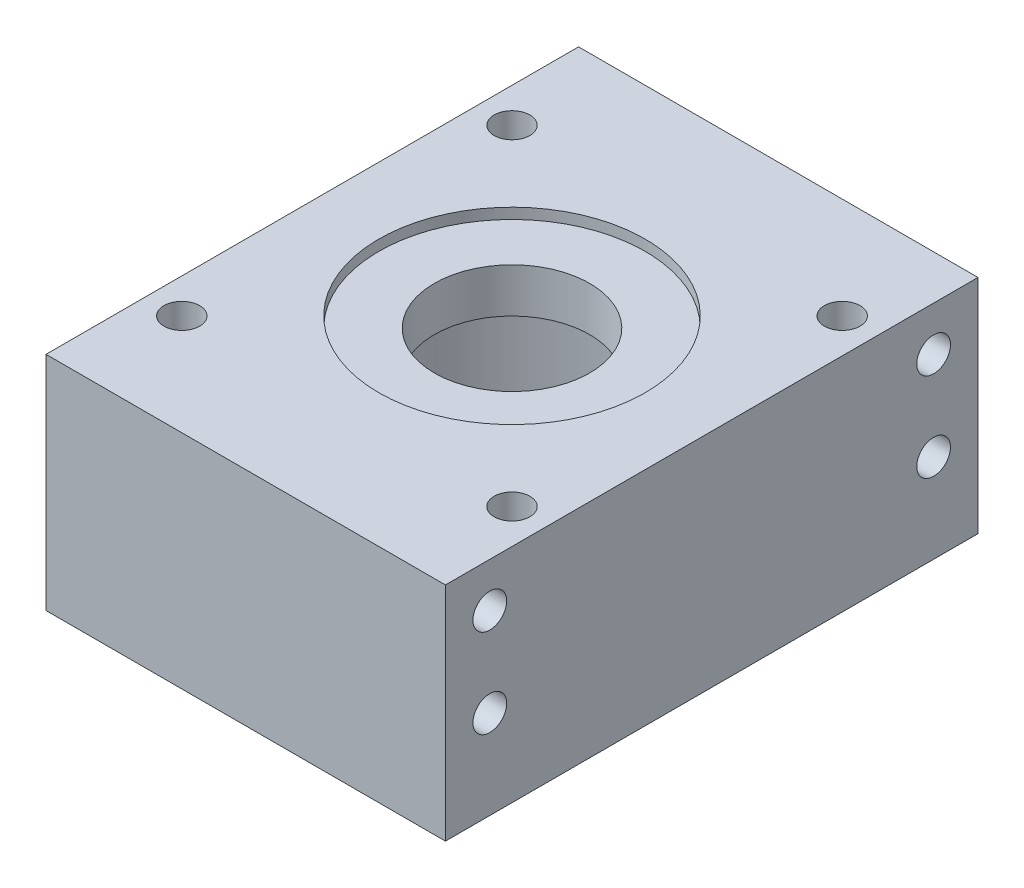
SolidWorks part; units mm, degrees
material "6061 Alloy"
ref_plane "Front" through (0, 0, 0) normal (0, 0, 1) x (1, 0, 0)
ref_plane "Top" through (0, 0, 0) normal (0, 1, 0) x (1, 0, 0)
ref_plane "Right" through (0, 0, 0) normal (1, 0, 0) x (0, 0, -1)
sketch "Sketch1" plane through (0, 0, 0) normal (0, 1, 0) x (1, 0, 0)
  line L0 (-28.575, 28.575) -> (-28.575, 38.1)
  line L1 (-28.575, 28.575) -> (28.575, 28.575) construction
  line L2 (-28.575, 28.575) -> (-28.575, -28.575)
  line L3 (-28.575, -28.575) -> (28.575, -28.575) construction
  line L4 (28.575, 28.575) -> (28.575, -28.575)
  line L5 (-28.575, 28.575) -> (28.575, -28.575) construction
  line L6 (-28.575, -28.575) -> (28.575, 28.575) construction
  line L7 (-23.622, 23.622) -> (23.622, 23.622) construction
  line L8 (-23.622, 23.622) -> (-23.622, -23.622) construction
  line L9 (-23.622, -23.622) -> (23.622, -23.622) construction
  line L10 (23.622, 23.622) -> (23.622, -23.622) construction
  line L11 (-23.622, 23.622) -> (23.622, -23.622) construction
  line L12 (-23.622, -23.622) -> (23.622, 23.622) construction
  line L13 (-28.575, 38.1) -> (28.575, 38.1)
  line L14 (28.575, 38.1) -> (28.575, 28.575)
  line L15 (-28.575, -28.575) -> (-28.575, -38.1)
  line L16 (-28.575, -38.1) -> (28.575, -38.1)
  line L17 (28.575, -38.1) -> (28.575, -28.575)
  circle A0 centre (23.622, -23.622) radius 2.5527
  circle A1 centre (23.622, 23.622) radius 2.5527
  circle A2 centre (-23.622, 23.622) radius 2.5527
  circle A3 centre (-23.622, -23.622) radius 2.5527
  point P0 (0, 0)
  point P6 (0, 0)
  dimension "D3" = 5.1054
  dimension "D1" = 57.15
  dimension "D2" = 47.244
  dimension "D4" = 9.525
extrude "Boss-Extrude1" add sketch "Sketch1" along normal blind 31.75
sketch "Sketch2" plane through (0, 31.75, 0) normal (0, 1, 0) x (1, 0, 0)
  circle A0 centre (0, 0) radius 19.05
  dimension "D1" = 38.1
extrude "Cut-Extrude1" cut sketch "Sketch2" against normal blind 1.524
sketch "Sketch3" plane through (0, 30.226, 0) normal (0, 1, 0) x (1, 0, 0)
  circle A0 centre (0, 0) radius 11.1125
  dimension "D1" = 22.225
extrude "Cut-Extrude2" cut sketch "Sketch3" against normal through all
sketch "Sketch4" plane through (0, 0, 0) normal (0, -1, 0) x (1, 0, 0)
  line L0 (0, 0) -> (0, 28.575) construction
  line L2 (0, 0) -> (13.0457, 20.2994) construction
  line L5 (-28.575, 28.575) -> (28.575, 28.575) construction
  circle A0 centre (0, 0) radius 21.844 construction
  circle A1 centre (0, 0) radius 24.13 construction
  arc A2 (0, 20.955) -> (2.8224, 22.6758) centre (0, 24.13) ccw
  arc A3 (11.3291, 17.6285) -> (9.8851, 20.602) centre (13.0457, 20.2994) cw
  arc A4 (2.8224, 22.6758) -> (9.8851, 20.602) centre (6.1542, 20.9592) cw
  arc A5 (11.3291, 17.6285) -> (14.6338, 17.5502) centre (13.0457, 20.2994) ccw
  arc A6 (14.6338, 17.5502) -> (19.4542, 11.9872) centre (16.5086, 14.3048) cw
  arc A7 (19.0613, 8.705) -> (19.4542, 11.9872) centre (21.9494, 10.024) cw
  arc A8 (19.0613, 8.705) -> (21.7991, 6.8525) centre (21.9494, 10.024) ccw
  arc A9 (21.7991, 6.8525) -> (22.8467, -0.4334) centre (21.6217, 3.1087) cw
  arc A10 (20.7417, -2.9822) -> (22.8467, -0.4334) centre (23.8844, -3.4341) cw
  arc A11 (20.7417, -2.9822) -> (22.0433, -6.0208) centre (23.8844, -3.4341) ccw
  arc A12 (22.0433, -6.0208) -> (18.9855, -12.7165) centre (19.87, -9.0743) cw
  arc A13 (15.8367, -13.7226) -> (18.9855, -12.7165) centre (18.2362, -15.8018) cw
  arc A14 (15.8367, -13.7226) -> (15.289, -16.9825) centre (18.2362, -15.8018) ccw
  arc A15 (15.289, -16.9825) -> (9.0966, -20.9621) centre (11.8098, -18.3763) cw
  arc A16 (5.9037, -20.1062) -> (9.0966, -20.9621) centre (6.7982, -23.1526) cw
  arc A17 (5.9037, -20.1062) -> (3.6804, -22.5524) centre (6.7982, -23.1526) ccw
  arc A18 (3.6804, -22.5524) -> (-3.6804, -22.5524) centre (0, -21.844) cw
  arc A19 (-5.9037, -20.1062) -> (-3.6804, -22.5524) centre (-6.7982, -23.1526) cw
  arc A20 (-5.9037, -20.1062) -> (-9.0966, -20.9621) centre (-6.7982, -23.1526) ccw
  arc A21 (-9.0966, -20.9621) -> (-15.289, -16.9825) centre (-11.8098, -18.3763) cw
  arc A22 (-15.8367, -13.7226) -> (-15.289, -16.9825) centre (-18.2362, -15.8018) cw
  arc A23 (-15.8367, -13.7226) -> (-18.9855, -12.7165) centre (-18.2362, -15.8018) ccw
  arc A24 (-18.9855, -12.7165) -> (-22.0433, -6.0208) centre (-19.87, -9.0743) cw
  arc A25 (-20.7417, -2.9822) -> (-22.0433, -6.0208) centre (-23.8844, -3.4341) cw
  arc A26 (-20.7417, -2.9822) -> (-22.8467, -0.4334) centre (-23.8844, -3.4341) ccw
  arc A27 (-22.8467, -0.4334) -> (-21.7991, 6.8525) centre (-21.6217, 3.1087) cw
  arc A28 (-19.0613, 8.705) -> (-21.7991, 6.8525) centre (-21.9494, 10.024) cw
  arc A29 (-19.0613, 8.705) -> (-19.4542, 11.9872) centre (-21.9494, 10.024) ccw
  arc A30 (-19.4542, 11.9872) -> (-14.6338, 17.5502) centre (-16.5086, 14.3048) cw
  arc A31 (-11.3291, 17.6285) -> (-14.6338, 17.5502) centre (-13.0457, 20.2994) cw
  arc A32 (-11.3291, 17.6285) -> (-9.8851, 20.602) centre (-13.0457, 20.2994) ccw
  arc A33 (-9.8851, 20.602) -> (-2.8224, 22.6758) centre (-6.1542, 20.9592) cw
  arc A34 (0, 20.955) -> (-2.8224, 22.6758) centre (0, 24.13) cw
  point P14 (0, 28.575)
  point P87 (0, 0)
  dimension "D1" = 48.26
  dimension "D2" = 43.688
  dimension "D4" = 3.175
  dimension "D5" = 3.175
  dimension "D3" = 32.727
  dimension "D6" = 11
extrude "Cut-Extrude3" cut sketch "Sketch4" against normal blind 23.876
sketch "Sketch5" plane through (0, 0, 0) normal (0, -1, 0) x (1, 0, 0)
  circle A0 centre (0, 0) radius 26.1937
  dimension "D1" = 52.3875
extrude "Cut-Extrude4" cut sketch "Sketch5" against normal blind 17.526
sketch "Sketch7" plane through (0, 0, 0) normal (0, -1, 0) x (1, 0, 0)
  line L0 (-28.575, -28.575) -> (28.575, -28.575) construction
  line L4 (-28.575, -38.1) -> (-28.575, 38.1) construction
  line L5 (-23.8125, 26.9875) -> (23.8125, 26.9875)
  line L6 (-26.9875, 23.8125) -> (-26.9875, -23.8125)
  line L7 (-23.8125, -26.9875) -> (23.8125, -26.9875)
  line L8 (26.9875, 23.8125) -> (26.9875, -23.8125)
  line L9 (-26.9875, 26.9875) -> (26.9875, -26.9875) construction
  line L10 (-26.9875, -26.9875) -> (26.9875, 26.9875) construction
  arc A0 (-26.9875, -23.8125) -> (-23.8125, -26.9875) centre (-23.8125, -23.8125) ccw
  arc A2 (23.8125, -26.9875) -> (26.9875, -23.8125) centre (23.8125, -23.8125) ccw
  arc A3 (23.8125, 26.9875) -> (26.9875, 23.8125) centre (23.8125, 23.8125) cw
  arc A4 (-23.8125, 26.9875) -> (-26.9875, 23.8125) centre (-23.8125, 23.8125) ccw
  point P0 (0, 0)
  dimension "D1" = 1.5875
  dimension "D3" = 3.175
  dimension "D2" = 1.5875
extrude "Cut-Extrude5" cut sketch "Sketch7" against normal blind 3.175
ref_plane "Plane1" through (0, 0, 28.575) normal (0, 0, 1) x (1, 0, 0)
hole_wizard "#10-32 Tapped Hole1" positions "Sketch9" profile "Sketch10" tap size "#10-32" standard "ANSI Inch" end condition through all
sketch "Sketch9" plane through (28.575, 0, 0) normal (1, 0, 0) x (0, 0, -1)
  line L0 (-38.1, 31.75) -> (38.1, 31.75) construction
  line L1 (-38.1, 0) -> (38.1, 0) construction
  line L2 (-38.1, 31.75) -> (-38.1, 0) construction
  line L3 (38.1, 31.75) -> (38.1, 0) construction
  point P0 (-31.75, 25.4)
  point P2 (-31.75, 12.7)
  point P4 (31.75, 12.7)
  point P6 (31.75, 25.4)
  dimension "D1" = 6.35
  dimension "D2" = 12.7
  dimension "D3" = 6.35
  dimension "D4" = 6.35
  dimension "D5" = 6.35
  dimension "D6" = 12.7
sketch "Sketch10" plane through (28.575, 25.4, 31.75) normal (0, 1, 0) x (0, 0, -1)
  line L0 (0, 0) -> (0, 57.15)
  line L1 (0, 57.15) -> (2.413, 57.15)
  line L2 (2.413, 57.15) -> (2.413, 0)
  line L5 (2.413, 0) -> (0, 0)
  line L11 (0, -6.35) -> (0, 107.95) construction
  dimension "Thread Major Dia." = 4.826
  dimension "Thru Tap Drill Depth" = 57.15
sketch "Sketch11" plane through (28.575, 0, 0) normal (1, 0, 0) x (0, 0, -1)
  line L0 (-38.1, 31.75) -> (38.1, 0) construction
  line L1 (-38.1, 0) -> (38.1, 0) construction
  line L2 (38.1, 31.75) -> (38.1, 0) construction
  point P7 (0, 15.875)
